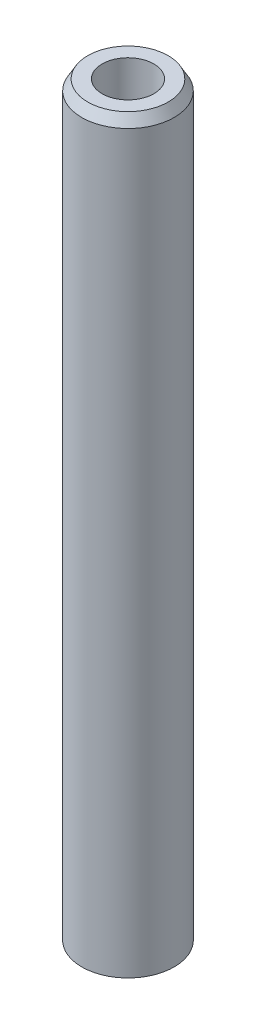
SolidWorks part; units mm, degrees
ref_plane "Front Plane" through (0, 0, 0) normal (0, 0, 1) x (1, 0, 0)
ref_plane "Top Plane" through (0, 0, 0) normal (0, 1, 0) x (1, 0, 0)
ref_plane "Right Plane" through (0, 0, 0) normal (1, 0, 0) x (0, 0, -1)
sketch "Sketch1" plane through (0, 0, 0) normal (0, 1, 0) x (1, 0, 0)
  circle A0 centre (0, 0) radius 7.5
  dimension "SHAFT_OD" = 15
extrude "Boss-Extrude1" add sketch "Sketch1" along normal blind 122.0537
sketch "Sketch2" plane through (0, 0, 0) normal (0, 1, 0) x (1, 0, 0)
  circle A0 centre (0, 0) radius 4.199
  dimension "BORE_D" = 8.3979
extrude "Cut-Extrude1" cut sketch "Sketch2" along normal through all
chamfer "Chamfer1" distance 1.6861 angle 30 2 edges at (0, 122.0537, 7.5) (0, 0, 7.5) first distance on face at (0, 122.0537, 7.5) first distance on face at (0, 0, 4.199)
